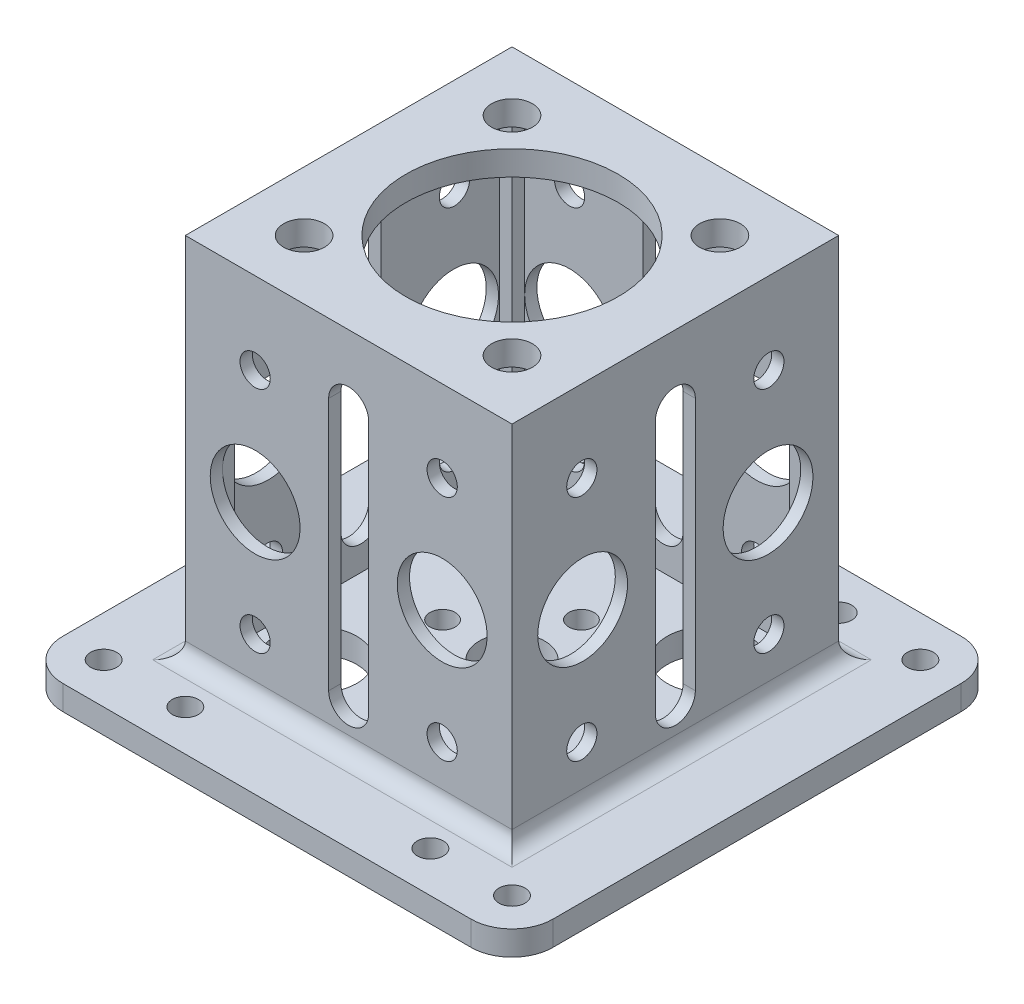
SolidWorks part; units mm, degrees
ref_plane "前视基准面" through (0, 0, 0) normal (0, 0, 1) x (1, 0, 0)
ref_plane "上视基准面" through (0, 0, 0) normal (0, 1, 0) x (1, 0, 0)
ref_plane "右视基准面" through (0, 0, 0) normal (1, 0, 0) x (0, 0, -1)
other "Configuration Table"
sketch "草图1" plane through (0, 0, 0) normal (0, 1, 0) x (1, 0, 0)
  line L0 (0, 8.5) -> (0, -8.5)
  line L1 (-20, 20) -> (20, 20)
  line L2 (-20, 20) -> (-20, -20)
  line L3 (-20, -20) -> (20, -20)
  line L4 (20, 20) -> (20, -20)
  line L5 (-20, 20) -> (20, -20) construction
  line L6 (-20, -20) -> (20, 20) construction
  line L7 (0, 0) -> (-20, 0) construction
  line L8 (-18.5, -18.5) -> (18.5, -18.5)
  line L9 (18.5, 18.5) -> (18.5, -18.5)
  line L10 (-18.5, 18.5) -> (18.5, 18.5)
  line L11 (-18.5, 18.5) -> (-18.5, -18.5)
  circle A0 centre (0, 0) radius 12.6
  circle A1 centre (0, 8.5) radius 1.55
  circle A3 centre (0, 0) radius 4
  circle A4 centre (8.5, 0) radius 1.55
  circle A5 centre (0, -8.5) radius 1.55
  circle A6 centre (-8.5, 0) radius 1.55
  point P0 (0, 0)
  point P11 (0, 0)
  point P23 (0, 0)
  dimension "D4" = 25.2
  dimension "D6" = 3.1
  dimension "D7" = 8
  dimension "D8" = 4
  dimension "D1" = 40
  dimension "D2" = 40
  dimension "D3" = 20
  dimension "D5" = 17
  dimension "D10" = 1.5
  dimension "D9" = 1.5
extrude "凸台-拉伸2" add sketch "草图1" against normal blind 3 contours L2 L3 L4 L1 | A6 | A5 | A1 | A4
extrude "切除-拉伸1" cut sketch "草图1<6>" against normal blind 1.5 contours L0 A3 | L0 A3 region at (1.6977, 0, 0) region at (-1.6977, 0, 0)
sketch "草图1<6>" plane through (0, 0, 0) normal (0, 1, 0) x (1, 0, 0) same geometry as "草图1"
sketch "草图2" plane through (0, 0, 0) normal (0, 1, 0) x (1, 0, 0)
  line L0 (-20, -20) -> (20, -20) construction
  line L1 (20, 20) -> (20, -20) construction
  line L2 (-20, 20) -> (-20, -20) construction
  line L3 (-20, 20) -> (20, 20) construction
  line L4 (-20, -20) -> (20, -20)
  line L5 (20, 20) -> (20, -20)
  line L6 (-20, 20) -> (-20, -20)
  line L7 (-20, 20) -> (20, 20)
  line L8 (0, 0) -> (38.7801, 0) construction
  line L9 (-20, 20) -> (-17, 20)
  line L10 (-20, 20) -> (-20, 17)
  line L11 (-20, 17) -> (-17, 17)
  line L12 (-17, 20) -> (-17, 17)
  line L13 (0, 0) -> (0, 17.8693) construction
  line L14 (20, -17) -> (17, -17)
  line L15 (20, 20) -> (17, 20)
  line L16 (20, 20) -> (20, 17)
  line L17 (20, 17) -> (17, 17)
  line L18 (17, 20) -> (17, 17)
  line L19 (17, -20) -> (17, -17)
  line L20 (20, -20) -> (17, -20)
  line L21 (20, -20) -> (20, -17)
  line L22 (-20, -20) -> (-20, -17)
  line L23 (-20, -20) -> (-17, -20)
  line L24 (-17, -20) -> (-17, -17)
  line L25 (-20, -17) -> (-17, -17)
  circle A0 centre (0, -8.5) radius 1.55 construction
  circle A1 centre (8.5, 0) radius 1.55 construction
  circle A2 centre (0, 8.5) radius 1.55 construction
  circle A3 centre (0, 0) radius 4 construction
  circle A4 centre (-8.5, 0) radius 1.55 construction
  circle A5 centre (0, -8.5) radius 1.55
  circle A6 centre (8.5, 0) radius 1.55
  circle A7 centre (0, 8.5) radius 1.55
  circle A8 centre (0, 0) radius 4
  circle A9 centre (-8.5, 0) radius 1.55
  point P35 (18.5, -17)
  line M9 (20, 20) -> (-20, 20)
  line M10 (-20, 20) -> (-20, -20)
  line M11 (-20, -20) -> (20, -20)
  line M12 (20, -20) -> (20, 20)
  dimension "D1" = 3
  dimension "D2" = 3
  dimension "D3" = 34
  dimension "D4" = 34
  dimension "D5" = 34
  dimension "D6" = 34
extrude "凸台-拉伸7" add sketch "草图2" along normal blind 45 contours L12 L7 L11 M10 | L18 L17 M9 M12 | L19 L4 L14 M12 | L25 L24 M10 M11 region at (-18.5, 0, 18.5) region at (18.5, 0, 18.5) region at (-18.5, 0, -18.5) region at (18.5, 0, -18.5)
sketch "草图5" plane through (-20, 0, 0) normal (-1, 0, 0) x (0, 0, 1)
  line L0 (20, -3) -> (20, 45) construction
  line L1 (-20, -3) -> (-20, 45) construction
  line L2 (20, -3) -> (20, 45)
  line L3 (-20, -3) -> (-20, 45)
  line L4 (-17, 0) -> (-17, 45)
  line L5 (-17, 45) -> (-17, 0) construction
  line L7 (-20, 45) -> (20, 45)
  line L8 (-20, 45) -> (-20, 42)
  line L9 (-20, 42) -> (20, 42)
  line L10 (20, 45) -> (20, 42)
extrude "凸台-拉伸8" add sketch "草图5" against normal blind 40 contours L8 L9 L10 L7
sketch "草图6" plane through (0, 45, 0) normal (0, 1, 0) x (1, 0, 0)
  line L0 (-20, -20) -> (0, -20)
  line L1 (0, -20) -> (0, 0)
  line L4 (20, -20) -> (20, 20)
  line L5 (20, 20) -> (-20, 20)
  line L6 (-20, 20) -> (-20, -20)
  line L7 (-20, -20) -> (20, -20)
  line L8 (20, -20) -> (20, 20)
  line L9 (20, 20) -> (-20, 20)
  line L10 (-20, 20) -> (-20, -20)
  line L11 (-20, -20) -> (20, -20)
  circle A0 centre (0, 0) radius 12.5
  dimension "D1" = 0
extrude "切除-拉伸2" cut sketch "草图6" against normal blind 4 contours A0 region at (-8.5888, 45, -8.5888)
sketch "草图7" plane through (0, -3, 0) normal (0, -1, 0) x (1, 0, 0)
  line L1 (-20, -20) -> (0, -20)
  line L2 (-20, -20) -> (-20, 0)
  line L3 (-20, 0) -> (0, 0)
  line L4 (-20, -20) -> (20, -20)
  line L5 (20, -20) -> (20, 20)
  line L6 (20, 20) -> (-20, 20)
  line L7 (-20, 20) -> (-20, -20)
  line L8 (-20, -20) -> (20, -20)
  line L9 (20, -20) -> (20, 20)
  line L10 (20, 20) -> (-20, 20)
  line L11 (-20, 20) -> (-20, -20)
  line L12 (0, -20) -> (0, 0)
  circle A0 centre (0, 0) radius 4
  dimension "D1" = 0
extrude "切除-拉伸3" cut sketch "草图7" against normal blind 4 contours L12 A0 L3 | L3 A0 L12 region at (-1.6977, -3, -1.6977) region at (0.5659, -3, 0.5659)
sketch "草图8" plane through (0, -3, 0) normal (0, -1, 0) x (1, 0, 0)
  line L0 (-20, 20) -> (0, 0) construction
  line L1 (0, 0) -> (20, 20) construction
  line L2 (-20, -20) -> (-20, 20) construction
  circle A0 centre (-12, 12) radius 5
  circle A1 centre (12, 12) radius 5
  circle A2 centre (12, -12) radius 5
  circle A3 centre (-12, -12) radius 5
  point P19 (0, 0)
  dimension "D1" = 8
  dimension "D2" = 4
extrude "切除-拉伸4" cut sketch "草图8" against normal blind 4
sketch "草图9" plane through (0, 45, 0) normal (0, 1, 0) x (1, 0, 0)
  line L0 (-20, 20) -> (0, 0) construction
  line L1 (0, 0) -> (20, 20) construction
  line L4 (20, -20) -> (20, 20)
  line L5 (20, 20) -> (-20, 20)
  line L6 (-20, 20) -> (-20, -20)
  line L7 (-20, -20) -> (20, -20)
  line L8 (20, -20) -> (20, 20)
  line L9 (20, 20) -> (-20, 20)
  line L10 (-20, 20) -> (-20, -20)
  line L11 (-20, -20) -> (20, -20)
  circle A0 centre (-12.7279, 12.7279) radius 2.5
  circle A1 centre (0, 0) radius 12.5 construction
  circle A2 centre (12.7279, 12.7279) radius 2.5
  circle A3 centre (12.7279, -12.7279) radius 2.5
  circle A4 centre (-12.7279, -12.7279) radius 2.5
  point P19 (0, 0)
  dimension "D2" = 18
  dimension "D3" = 4
  dimension "D1" = 0
extrude "切除-拉伸5" cut sketch "草图9" against normal blind 4 contours A0 | A4 | A2 | A3
sketch "草图10" plane through (0, 0, 0) normal (0, 1, 0) x (1, 0, 0)
  line L0 (20, -17) -> (17, -17) construction
  line L1 (20, 17) -> (18.5, 17)
  line L2 (20, 17) -> (20, -17)
  line L3 (20, -17) -> (18.5, -17)
  line L4 (18.5, 17) -> (18.5, -17)
  line L5 (17, -20) -> (-17, -20)
  line L6 (17, -20) -> (17, -18.5)
  line L7 (17, -18.5) -> (-17, -18.5)
  line L8 (-17, -20) -> (-17, -18.5)
  line L9 (-20, -17) -> (-20, 17)
  line L10 (-20, -17) -> (-18.5, -17)
  line L11 (-18.5, -17) -> (-18.5, 17)
  line L12 (-20, 17) -> (-18.5, 17)
  line L13 (-17, 20) -> (17, 20)
  line L14 (-17, 20) -> (-17, 18.5)
  line L15 (-17, 18.5) -> (17, 18.5)
  line L16 (17, 20) -> (17, 18.5)
  point P25 (0, 0)
  dimension "D1" = 4
extrude "凸台-拉伸10" add sketch "草图10" along normal blind 45
sketch "草图20" plane through (0, 0, 18.5) normal (0, 0, -1) x (-1, 0, 0)
  line L0 (0, 0) -> (0, 42)
  line L1 (-17, 0) -> (17, 0) construction
  line L2 (-20, -3) -> (-20, 45) construction
  line L3 (0, 0) -> (0, 3)
  line L4 (0, 3) -> (0, 5.5)
  line L5 (0, 21) -> (4.1437, 21)
  line L6 (-2.45, 36.5) -> (-2.45, 5.5)
  line L7 (2.45, 36.5) -> (2.45, 5.5)
  line L8 (-20, 45) -> (20, 45) construction
  line L9 (20, -3) -> (-20, -3) construction
  arc A1 (-2.45, 5.5) -> (2.45, 5.5) centre (0, 5.5) ccw
  arc A2 (-2.45, 36.5) -> (2.45, 36.5) centre (0, 36.5) cw
  point P10 (0, 45)
  point P13 (0, 38.95)
  point P20 (0, -3)
  point P21 (0, 3)
  dimension "D1" = 90
  dimension "D3" = 2.45
  dimension "D2" = 20
  dimension "D4" = 5.5
extrude "切除-拉伸12" cut sketch "草图20" against normal blind 4 and the other way through all contours L7 A1 L6 A2
sketch "草图24" plane through (20, 0, 0) normal (1, 0, 0) x (0, 0, -1)
  line L0 (0, -3) -> (0, 3)
  line L1 (0, 21) -> (-20, 21) construction
  line L2 (20, -3) -> (-20, -3) construction
  line L3 (0, 3) -> (0, 5.5)
  line L4 (0, -3) -> (0, 0)
  line L5 (0, 0) -> (0, 42)
  line L6 (0, 21) -> (5.4047, 21)
  line L7 (-2.45, 36.5) -> (-2.45, 5.5)
  line L8 (2.45, 5.5) -> (2.45, 36.5)
  line L9 (-20, 45) -> (20, 45) construction
  line L12 (-11.35, -3) -> (-11.35, 45) construction
  line L13 (-11.35, 21) -> (-11.35, 49) construction
  line L16 (20, -3) -> (20, 45)
  line L17 (20, 45) -> (-20, 45)
  line L18 (-20, 45) -> (-20, -3)
  line L19 (-20, -3) -> (20, -3)
  line L20 (20, -3) -> (20, 45)
  line L21 (20, 45) -> (-20, 45)
  line L22 (-20, 45) -> (-20, -3)
  line L23 (-20, -3) -> (20, -3)
  arc A0 (-2.45, 5.5) -> (2.45, 5.5) centre (0, 5.5) ccw
  arc A1 (-2.45, 36.5) -> (2.45, 36.5) centre (0, 36.5) cw
  circle A2 centre (-11.45, 35) radius 1.85
  circle A3 centre (-11.45, 7) radius 1.85
  circle A4 centre (11.45, 7) radius 1.85
  circle A5 centre (11.45, 35) radius 1.85
  circle A6 centre (-11.35, 21) radius 5.5
  circle A7 centre (11.35, 21) radius 5.5
  point P7 (0, 38.95)
  point P13 (0, 45)
  point P18 (0, 3.05)
  point P37 (-11.45, 35)
  dimension "D1" = 3
  dimension "D3" = 9
  dimension "D4" = 3.7
  dimension "D6" = 10
  dimension "D7" = 8.65
  dimension "D8" = 2.45
  dimension "D2" = 8.5
  dimension "D5" = 0
extrude "切除-拉伸13" cut sketch "草图24" along normal blind 4 and the other way through all contours L7 A0 L8 A1
extrude "切除-拉伸15" cut sketch "草图24<5>" along normal blind 10 and the other way through all contours A2 | A5 | A6 | A7 | A3 | A4
sketch "草图24<5>" plane through (20, 0, 0) normal (1, 0, 0) x (0, 0, -1) same geometry as "草图24"
sketch "草图25" plane through (0, 0, -20) normal (0, 0, -1) x (-1, 0, 0)
  line L0 (-11.45, -3) -> (-11.45, 45) construction
  line L1 (-2.45, 36.5) -> (-2.45, 5.5) construction
  line L2 (-11.45, 21) -> (-31.2071, 21) construction
  line L3 (-11.45, 45) -> (-11.45, 35) construction
  line L4 (20, -3) -> (20, 45)
  line L5 (20, 45) -> (-20, 45)
  line L6 (-20, 45) -> (-20, -3)
  line L7 (-20, -3) -> (20, -3)
  line L8 (20, -3) -> (20, 45)
  line L9 (20, 45) -> (-20, 45)
  line L10 (-20, 45) -> (-20, -3)
  line L11 (-20, -3) -> (20, -3)
  line L12 (0, 0) -> (0, 45) construction
  line L13 (-2.45, 36.5) -> (-2.45, 5.5)
  circle A0 centre (-11.45, 21) radius 5.5
  circle A1 centre (-11.45, 35) radius 1.85
  circle A2 centre (11.45, 35) radius 1.85
  circle A3 centre (11.45, 7) radius 1.85
  circle A4 centre (-11.45, 7) radius 1.85
  circle A5 centre (11.45, 21) radius 5.5
  dimension "D3" = 10
  dimension "D4" = 11
  dimension "D2" = 9
  dimension "D1" = 0
extrude "切除-拉伸16" cut sketch "草图25" along normal blind 10 and the other way through all contours A0 | A5 | A1 | A4 | A3 | A2 region at (11.45, 21, -20) region at (-11.45, 21, -20)
sketch "草图26" plane through (0, 0, -20) normal (0, 0, -1) x (-1, 0, 0)
sketch "草图27" plane through (0, -3, 0) normal (0, -1, 0) x (1, 0, 0)
  line L0 (0, -1000) -> (0, 49000) construction
  line L1 (-30, -30) -> (30, -30)
  line L2 (-30, -30) -> (-30, 30)
  line L3 (-30, 30) -> (30, 30)
  line L4 (30, -30) -> (30, 30)
  line L5 (-30, -30) -> (30, 30) construction
  line L6 (-30, 30) -> (30, -30) construction
  line L7 (-25, -25) -> (25, -25)
  line L8 (-25, -25) -> (-25, 25)
  line L9 (-25, 25) -> (25, 25)
  line L10 (25, -25) -> (25, 25)
  line L11 (-25, -25) -> (25, 25) construction
  line L12 (-25, 25) -> (25, -25) construction
  line L13 (-1000, 0) -> (49000, 0) construction
  line L14 (-10, 0) -> (-10, 25)
  line L15 (-10, 25) -> (-15, 25)
  circle A0 centre (-25, 25) radius 1.6
  circle A1 centre (25, 25) radius 1.6
  circle A2 centre (25, -25) radius 1.6
  circle A3 centre (-25, -25) radius 1.6
  circle A4 centre (0, 0) radius 10
  circle A5 centre (-15, 25) radius 1.6
  circle A6 centre (15, 25) radius 1.6
  circle A7 centre (15, -25) radius 1.6
  circle A8 centre (-15, -25) radius 1.6
  point P0 (0, 0)
  point P6 (0, 0)
  point P21 (0, 0)
  line M17 (-20, -20) -> (20, -20)
  line M18 (20, -20) -> (20, 20)
  line M19 (20, 20) -> (-20, 20)
  line M20 (-20, 20) -> (-20, -20)
  dimension "D5" = 3.2
  dimension "D7" = 20
  dimension "D9" = 3.2
  dimension "D1" = 60
  dimension "D2" = 60
  dimension "D3" = 50
  dimension "D4" = 50
  dimension "D8" = 5
  dimension "D6" = 4
extrude "凸台-拉伸13" add sketch "草图27" against normal blind 3 contours L7 A8 A7 A2 L10 A1 L9 A6 L15 A5 A0 L8 A3 M19 M18 M17 M20 | L1 L4 L3 L2 L7 A8 A3 L8 A0 L9 A5 L15 A6 A1 L10 A2 A7 region at (-29.1515, -3, 0) region at (-23.3686, -3, -23.3686)
fillet "圆角1" radius 2 4 edges at (0, 0, 20) (-20, 0, 0) (20, 0, 0) (0, 0, -20)
fillet "圆角2" radius 5 4 edges at (-30, -1.5, 30) (30, -1.5, 30) (30, -1.5, -30) (-30, -1.5, -30)
sketch "草图28" plane through (0, 45, 0) normal (0, 1, 0) x (1, 0, 0)
  circle A0 centre (0, 0) radius 13
  dimension "D1" = 26
extrude "切除-拉伸17" cut sketch "草图28" against normal blind 10
